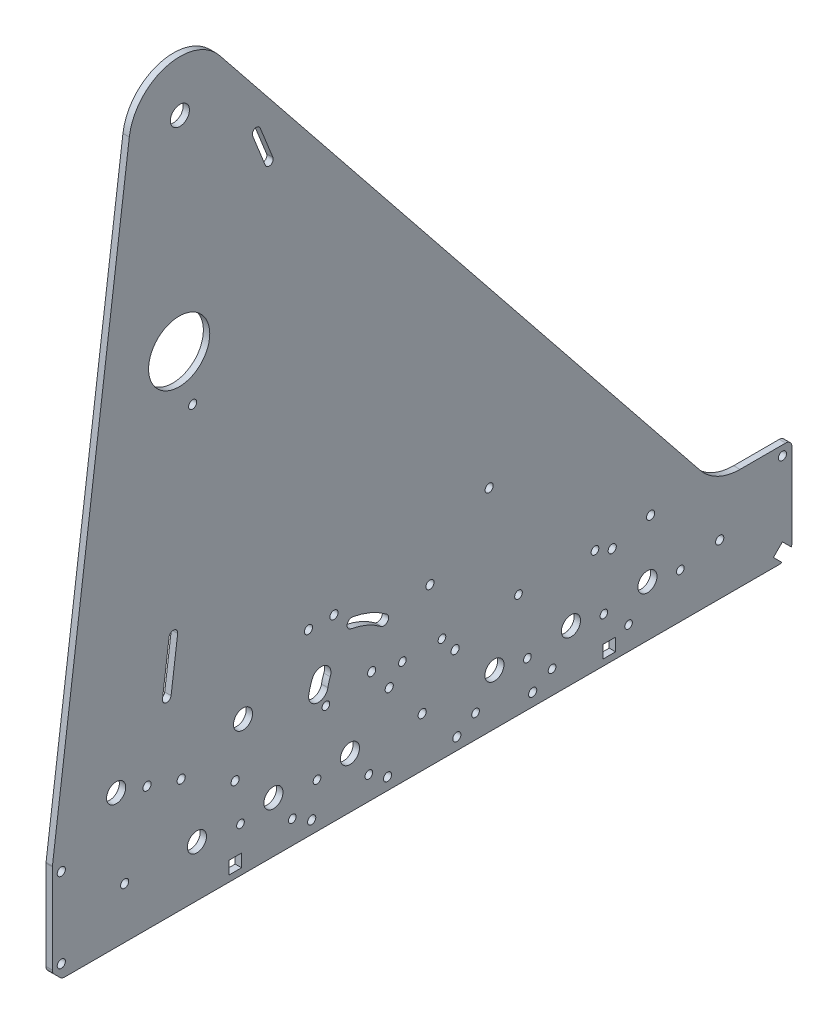
SolidWorks part; units mm, degrees
ref_plane "Front Plane" through (0, 0, 0) normal (0, 0, 1) x (1, 0, 0)
ref_plane "Top Plane" through (0, 0, 0) normal (0, 1, 0) x (1, 0, 0)
ref_plane "Right Plane" through (0, 0, 0) normal (1, 0, 0) x (0, 0, -1)
sketch "Sketch1" plane through (0, 0, 0) normal (1, 0, 0) x (0, 0, -1)
  line L0 (-184.15, -24.6062) -> (184.15, -24.6062)
  line L1 (184.15, -24.6062) -> (184.15, 26.1938)
  line L2 (184.15, 26.1938) -> (146.05, 26.1937)
  line L5 (-145.839, 321.5609) -> (-184.15, 26.1938)
  line L6 (-184.15, 26.1938) -> (-184.15, -24.6062)
  line L7 (-184.15, 350.0437) -> (184.15, 350.0437) construction
  line L9 (146.05, 26.1937) -> (-100.8314, 334.1803)
  arc A0 (-100.8314, 334.1803) -> (-145.839, 321.5609) centre (-120.65, 318.2937) ccw
  point P8 (0, -24.6062)
  dimension "D1" = 368.3
  dimension "D7" = 25.4
  dimension "D2" = 50.8
  dimension "D3" = 38.1
  dimension "D4" = 24.6062
  dimension "D5" = 374.65
  dimension "D6" = 304.8
  dimension "D8" = 342.9
extrude "Boss-Extrude1" add sketch "Sketch1" along normal blind 3.175
chamfer "Chamfer1" distance 4.7625 angle 45 2 edges at (1.5875, -24.6062, 184.15) (1.5875, -24.6062, -184.15)
fillet "Fillet1" radius 25.4 1 edges at (1.5875, 26.1937, -146.05)
fillet "Fillet2" radius 3.175 2 edges at (1.5875, 26.1938, 184.15) (1.5875, 26.1938, -184.15)
fillet "Fillet3" radius 3.175 4 edges at (1.5875, -19.8438, -184.15) (1.5875, -24.6062, -179.3875) (1.5875, -19.8437, 184.15) (1.5875, -24.6062, 179.3875)
sketch "Sketch30" plane through (3.175, 0, 0) normal (1, 0, 0) x (0, 0, -1)
  circle A8 centre (-89.211, 42.2593) radius 4.7625
  circle A9 centre (-25.1593, 30.6938) radius 2.032
  arc A10 (-51.7173, 35.4892) -> (-50.2741, 40.5715) centre (-25.1593, 30.6938) cw construction
  arc A11 (-54.7652, 42.3379) -> (-56.4665, 36.3468) centre (-25.1593, 30.6938) ccw
  arc A12 (-45.783, 38.8051) -> (-46.9681, 34.6317) centre (-25.1593, 30.6938) ccw
  arc A13 (-45.783, 38.8051) -> (-54.7652, 42.3379) centre (-50.2741, 40.5715) ccw
  arc A14 (-56.4665, 36.3468) -> (-46.9681, 34.6317) centre (-51.7173, 35.4892) ccw
  arc A15 (-34.9881, 56.6661) -> (-19.1131, 49.8125) centre (-41.7582, 19.1724) cw construction
  arc A16 (-17.6789, 51.753) -> (-34.5594, 59.0407) centre (-41.7582, 19.1724) ccw
  arc A17 (-20.5473, 47.8719) -> (-35.4169, 54.2915) centre (-41.7582, 19.1724) ccw
  arc A18 (-20.5473, 47.8719) -> (-17.6789, 51.753) centre (-19.1131, 49.8125) ccw
  arc A19 (-34.5594, 59.0407) -> (-35.4169, 54.2915) centre (-34.9881, 56.6661) ccw
  arc A20 (-19.1131, 49.8125) -> (-34.9881, 56.6661) centre (-41.7582, 19.1724) ccw construction
  circle A21 centre (94.6345, 23.8125) radius 2.032
  circle A22 centre (-56.6241, 64.5541) radius 2.032
  circle A23 centre (-43.9241, 64.5541) radius 2.032
  circle A24 centre (-56.6241, 64.5541) radius 1.905 construction
  circle A25 centre (-43.9241, 64.5541) radius 1.905 construction
  point P7 (-51.1204, 38.0658)
  point P19 (-26.6567, 54.1518)
  dimension "D2" = 9.652
  dimension "D4" = 4.064
  dimension "D1" = 4.064
  dimension ".375" = 9.525
  dimension "D3" = 4.826
extrude "Cut-Extrude9" cut sketch "Sketch30" against normal through all
sketch "Sketch16" plane through (3.175, 0, 0) normal (1, 0, 0) x (0, 0, -1)
  circle A0 centre (112.1746, 0.7937) radius 4.7625
  circle A1 centre (74.0746, 0.7937) radius 4.7625
  circle A2 centre (35.9746, 0.7937) radius 4.7625
  circle A3 centre (-35.9746, 0.7938) radius 4.7625
  circle A4 centre (-74.0746, 0.7938) radius 4.7625
  circle A5 centre (-112.1746, 0.7937) radius 4.7625
  dimension "D1" = 9.525
  dimension "D2" = 9.525
extrude "Cut-Extrude1" cut sketch "Sketch16" against normal up to next
sketch "Sketch25" plane through (3.175, 0, 0) normal (1, 0, 0) x (0, 0, -1)
  circle A0 centre (102.7672, -13.0003) radius 1.905 construction
  circle A1 centre (86.0486, 27.3622) radius 1.905 construction
  circle A2 centre (128.5804, -2.3081) radius 1.905 construction
  circle A3 centre (102.7672, -13.0003) radius 1.905
  circle A4 centre (86.0486, 27.3622) radius 1.905
  circle A5 centre (128.5804, -2.3081) radius 1.905
  circle A6 centre (64.6672, -13.0003) radius 1.905 construction
  circle A8 centre (-9.8486, 27.3622) radius 1.905 construction
  circle A10 centre (-47.9486, 27.3622) radius 1.905 construction
  circle A11 centre (-90.4804, -2.3081) radius 1.905 construction
  circle A12 centre (-64.6672, -13.0003) radius 1.905 construction
  circle A14 centre (-52.3804, -2.3081) radius 1.905 construction
  circle A15 centre (-26.5672, -13.0003) radius 1.905 construction
  circle A16 centre (9.8486, 27.3622) radius 1.905 construction
  circle A17 centre (26.5672, -13.0003) radius 1.905 construction
  circle A18 centre (47.9486, 27.3622) radius 1.905 construction
  circle A19 centre (52.3804, -2.3081) radius 1.905 construction
  circle A20 centre (90.4804, -2.3081) radius 1.905 construction
  circle A21 centre (-9.8486, 27.3622) radius 1.905
  circle A23 centre (-47.9486, 27.3622) radius 1.905
  circle A24 centre (-90.4804, -2.3081) radius 1.905
  circle A25 centre (-64.6672, -13.0003) radius 1.905
  circle A27 centre (-52.3804, -2.3081) radius 1.905
  circle A28 centre (-26.5672, -13.0003) radius 1.905
  circle A29 centre (9.8486, 27.3622) radius 1.905
  circle A30 centre (26.5672, -13.0003) radius 1.905
  circle A31 centre (47.9486, 27.3622) radius 1.905
  circle A32 centre (64.6672, -13.0003) radius 1.905
  circle A33 centre (52.3804, -2.3081) radius 1.905
  circle A34 centre (90.4804, -2.3081) radius 1.905
extrude "Cut-Extrude4" cut sketch "Sketch25" against normal up to next
sketch "Sketch23" plane through (3.175, 0, 0) normal (1, 0, 0) x (0, 0, -1)
  point P0 (-55.0246, -18.3223)
  point P6 (-93.1246, 17.5943)
  point P9 (-17.2515, -18.6426)
  point P12 (-16.4124, 19.3854)
  point P15 (16.4124, 19.3854)
  point P18 (17.2515, -18.6426)
  point P21 (55.0246, -18.3223)
  point P35 (3.8736, 53.6853)
  point P38 (113.7728, 28.6594)
  point P41 (-137.0088, 37.226)
  point P44 (-179.705, 21.7487)
  point P47 (-179.705, -18.0026)
  point P50 (179.3875, 21.4312)
hole_wizard "#8 (0.16) Diameter Hole1" positions "Sketch23" profile "Sketch24" hole size "#8" standard "ANSI Inch" end condition up to next
sketch "Sketch24" plane through (3.175, -18.3223, 55.0246) normal (0, 1, 0) x (0, 0, -1)
  line L0 (0, 0) -> (0, 3.175)
  line L1 (0, 3.175) -> (2.032, 3.175)
  line L2 (2.032, 3.175) -> (2.032, 0)
  line L5 (2.032, 0) -> (0, 0)
  line L11 (0, -6.35) -> (0, 107.95) construction
  dimension "Thru Hole Dia." = 4.064
  dimension "Thru Hole Depth" = 3.175
sketch "Sketch22" plane through (3.175, 0, 0) normal (1, 0, 0) x (0, 0, -1)
  line L0 (-96.2996, -15.1473) -> (-89.9496, -15.1473) construction
  line L1 (-96.2996, -15.1473) -> (-89.9496, -15.1473)
  line L2 (-96.2996, -15.1473) -> (-96.2996, -21.4973)
  line L3 (-96.2996, -21.4973) -> (-89.9496, -21.4973)
  line L4 (-89.9496, -15.1473) -> (-89.9496, -21.4973)
  line L5 (-96.2996, -15.1473) -> (-89.9496, -21.4973) construction
  line L6 (-96.2996, -21.4973) -> (-89.9496, -15.1473) construction
  line L7 (-89.9496, -15.1473) -> (-89.9496, -19.8734) construction
  line L77 (179.3875, -24.6062) -> (183.8776, -20.1161)
  line L78 (179.3875, -24.6062) -> (174.8974, -20.1161)
  line L79 (183.8776, -20.1161) -> (179.3875, -15.626)
  line L80 (174.8974, -20.1161) -> (179.3875, -15.626)
  line L81 (180.3174, -23.6763) -> (183.2201, -20.7737) construction
  line L82 (-178.0724, -24.6062) -> (178.0724, -24.6062) construction
  line L84 (89.9496, -21.4973) -> (96.2996, -21.4973)
  line L85 (89.9496, -21.4973) -> (89.9496, -15.1473)
  line L86 (89.9496, -15.1473) -> (96.2996, -15.1473)
  line L87 (96.2996, -21.4973) -> (96.2996, -15.1473)
  line L88 (89.9496, -21.4973) -> (96.2996, -15.1473) construction
  line L89 (89.9496, -15.1473) -> (96.2996, -21.4973) construction
  point P0 (-93.1246, -18.3223)
  point P19 (93.1246, -18.3223)
  dimension "D1" = 6.35
  dimension "D2" = 6.35
extrude "Cut-Extrude3" cut sketch "Sketch22" against normal up to next
sketch "Sketch21" plane through (3.175, 0, 0) normal (1, 0, 0) x (0, 0, -1)
  circle A0 centre (-148.1579, 0.7937) radius 2.032
  circle A2 centre (0, 0) radius 2.032
  circle A3 centre (148.1579, 0.7938) radius 2.032
  dimension "D1" = 4.064
extrude "Cut-Extrude2" cut sketch "Sketch21" against normal up to next
sketch "Sketch26" plane through (3.175, 0, 0) normal (1, 0, 0) x (0, 0, -1)
  line L0 (-145.839, 321.5609) -> (-184.1236, 26.3971) construction
  line L1 (-178.0724, -24.6062) -> (178.0724, -24.6062) construction
  circle A0 centre (-121.0218, 216.6937) radius 15.24
  dimension "D1" = 30.48
  dimension "D2" = 38.1
  dimension "D3" = 241.3
extrude "Cut-Extrude5" cut sketch "Sketch26" against normal through all
sketch "Sketch27" plane through (3.175, 0, 0) normal (1, 0, 0) x (0, 0, -1)
  circle A0 centre (-120.65, 318.2937) radius 4.7625
  dimension "D1" = 9.525
extrude "Cut-Extrude6" cut sketch "Sketch27" against normal through all
sketch "Sketch28" plane through (3.175, 0, 0) normal (1, 0, 0) x (0, 0, -1)
  line L0 (-120.65, 318.2937) -> (-103.5612, 277.2599) construction
  line L1 (-103.5612, 277.2599) -> (-86.3654, 258.566) construction
  line L2 (-86.3654, 258.566) -> (-90.1612, 246.4465) construction
  line L3 (-90.1612, 246.4465) -> (-93.9569, 234.327) construction
  line L4 (-145.839, 321.5609) -> (-184.1236, 26.3971) construction
  circle A0 centre (-93.9569, 234.327) radius 2.032
  circle A1 centre (-90.1612, 246.4465) radius 2.032
  circle A2 centre (-86.3654, 258.566) radius 2.0955
  circle A3 centre (-103.5612, 277.2599) radius 2.032
  dimension "D4" = 4.064
  dimension "D5" = 4.191
  dimension "D6" = 4.064
  dimension "D1" = 25.4
  dimension "D2" = 44.45
  dimension "D3" = 12.7
  dimension "D7" = 30
  dimension "D8" = 120
  dimension "D9" = 160
extrude "Cut-Extrude7" [suppressed] cut sketch "Sketch28" against normal through all
sketch "Sketch29" plane through (3.175, 0, 0) normal (1, 0, 0) x (0, 0, -1)
  line L1 (-82.55, 292.1) -> (-76.2, 276.225) construction
  line L2 (-80.6633, 292.8547) -> (-74.3133, 276.9797)
  line L3 (-84.4367, 291.3453) -> (-78.0867, 275.4703)
  arc A4 (-80.6633, 292.8547) -> (-84.4367, 291.3453) centre (-82.55, 292.1) ccw
  arc A5 (-78.0867, 275.4703) -> (-74.3133, 276.9797) centre (-76.2, 276.225) ccw
  point P8 (-79.375, 284.1625)
  dimension "D1" = 276.225
  dimension "D2" = 2.032
  dimension "D3" = 76.2
  dimension "D4" = 82.55
  dimension "D5" = 292.1
sketch "Sketch31" plane through (0, 0, 0) normal (-1, 0, 0) x (0, 0, 1)
  circle A1 centre (114.3, 190.5) radius 2.032
  dimension "D1" = 114.3
  dimension "D6" = 4.064
  dimension "D2" = 190.5
extrude "Cut-Extrude10" cut sketch "Sketch31" against normal through all
sketch "Sketch34" plane through (0, 0, 0) normal (-1, 0, 0) x (0, 0, 1)
  line L3 (123.9045, 95.7355) -> (127.1716, 70.5465) construction
  line L4 (126.0455, 96.0132) -> (129.3127, 70.8242)
  line L5 (121.7634, 95.4578) -> (125.0306, 70.2688)
  line L6 (145.839, 321.5609) -> (184.1236, 26.3971) construction
  arc A2 (126.0455, 96.0132) -> (121.7634, 95.4578) centre (123.9045, 95.7355) ccw
  arc A3 (125.0306, 70.2688) -> (129.3127, 70.8242) centre (127.1716, 70.5465) ccw
  point P9 (125.538, 83.141)
  point P18 (114.3, 190.5)
  dimension "D8" = 4.318
  dimension "D6" = 50.8
  dimension "D7" = 25.4
  dimension "D9" = 95.25
extrude "Cut-Extrude12" cut sketch "Sketch34" against normal through all
sketch "Sketch37" plane through (3.175, 0, 0) normal (1, 0, 0) x (0, 0, -1)
  circle A0 centre (33.3375, 80.645) radius 2.032
  circle A8 centre (0, 0) radius 2.032 construction
  dimension "D1" = 4.064
  dimension "D2" = 33.3375
  dimension "D3" = 80.645
extrude "Cut-Extrude13" cut sketch "Sketch37" against normal through all
sketch "Sketch38" plane through (3.175, 0, 0) normal (1, 0, 0) x (0, 0, -1)
  line L0 (-184.15, 25.9887) -> (-184.15, -18.5286) construction
  line L1 (-178.0724, -24.6062) -> (178.0724, -24.6062) construction
  circle A0 centre (-152.4, 42.0688) radius 4.7625
  dimension "D1" = 31.75
  dimension "D3" = 9.525
  dimension "D2" = 66.675
extrude "Cut-Extrude14" cut sketch "Sketch38" against normal through all
extrude "Cut-Extrude15" cut sketch "Sketch29" against normal through all
sketch "Sketch40" plane through (3.175, 0, 0) normal (1, 0, 0) x (0, 0, -1)
  circle A0 centre (-120.015, 31.75) radius 2.032
  dimension "D1" = 4.064
  dimension "D2" = 120.015
  dimension "D3" = 31.75
extrude "Cut-Extrude16" cut sketch "Sketch40" against normal through all
